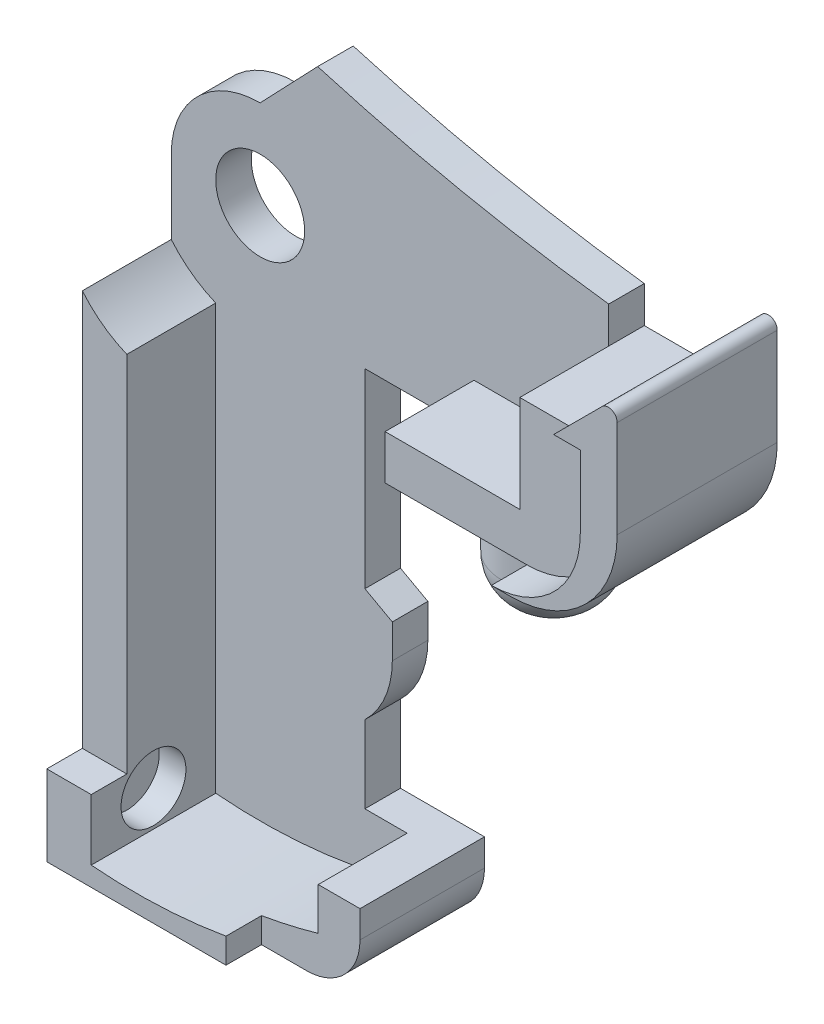
SolidWorks part; units mm, degrees
ref_plane "정면" through (0, 0, 0) normal (0, 0, 1) x (1, 0, 0)
ref_plane "윗면" through (0, 0, 0) normal (0, 1, 0) x (1, 0, 0)
ref_plane "우측면" through (0, 0, 0) normal (1, 0, 0) x (0, 0, -1)
sketch "스케치1" plane through (0, 0, 0) normal (0, 0, 1) x (1, 0, 0)
  line L0 (0, 5) -> (3.2319, 8.3833)
  line L1 (0, 5) -> (19.6, 5)
  line L2 (19.6, 5) -> (19.6, 2.9507)
  line L3 (19.6, 2.9507) -> (23.5, 2.9507)
  line L4 (23.5, 2.9507) -> (23.5, 4.0959)
  line L5 (23.5, 4.0959) -> (25, 4.0959)
  line L6 (25, 4.0959) -> (25, 0)
  line L7 (20, -5) -> (5.8894, -5)
  line L8 (5.8894, -5) -> (5.8894, -26.4376)
  line L9 (-5, -30.9618) -> (7.6137, -30.9618)
  line L10 (-5, -30.9618) -> (-5, 0)
  line L11 (10.6137, -27.9618) -> (10.6137, -26.4376)
  line L12 (10.6137, -26.4376) -> (5.8894, -26.4376)
  line L13 (5.8894, -26.4376) -> (8.2516, -26.4376)
  line L14 (19.6, 2.9507) -> (19.6, -2.5)
  line L15 (19.6, -2.5) -> (12.0232, -2.5)
  line L16 (-2.5, -4.3301) -> (-2.5, -26.4377)
  line L17 (-2.5, -29.8745) -> (-2.5, -26.4377)
  line L18 (-2.5, -26.4377) -> (-5, -26.4377)
  line L19 (5.0761, -29.546) -> (5.0761, -30.9618)
  line L20 (5.8894, -15.7188) -> (5.8894, -26.4376)
  line L21 (8.2649, -26.4376) -> (8.2649, -28.8171)
  line L22 (12.0232, -2.5) -> (12.0232, -5)
  line L23 (5.8894, -15.7188) -> (5.8894, -26.4376)
  line L24 (7.4303, -18.4599) -> (7.4303, -16.5644)
  line L25 (7.4303, -16.5644) -> (5.8894, -15.7188)
  line L26 (23.5, 4.0959) -> (26.2222, 6.8181)
  line L27 (27.0757, 6.4645) -> (27.0757, 1)
  line L28 (21.0757, -5) -> (20, -5)
  circle A0 centre (0, 0) radius 2.5
  circle A1 centre (0, 0) radius 5
  arc A2 (-2.5, -29.8745) -> (8.2649, -28.8171) centre (0, 0) ccw
  arc A3 (-5, -4.1533) -> (-2.5, -6) centre (0, 0) ccw
  arc A4 (19.6, 5) -> (3.2319, 8.3833) centre (32.2465, 107.4683) cw
  arc A5 (25, 0) -> (20, -5) centre (20, 0) cw
  arc A6 (7.4303, -18.4599) -> (5.8894, -22.0908) centre (2.3818, -18.4599) cw
  arc A7 (7.6137, -30.9618) -> (10.6137, -27.9618) centre (7.6137, -27.9618) ccw
  arc A8 (27.0757, 1) -> (21.0757, -5) centre (21.0757, 1) cw
  arc A9 (26.2222, 6.8181) -> (27.0757, 6.4645) centre (26.5757, 6.4645) cw
  point P48 (27.0757, 7.6716)
  dimension "D1" = 5
  dimension "D2" = 19.6
  dimension "D3" = 5
  dimension "D6" = 3
  dimension "D9" = 6
  dimension "D10" = 0.5
  dimension "D4" = 30
  dimension "D5" = 1.5
  dimension "D7" = 5.0568
  dimension "D8" = 45
extrude "보스-돌출3" add sketch "스케치1" along normal blind 9 contours A2 L17 L18 L10 L9 L19 | A9 L26 L5 L6 A5 L28 A8 L27 region at (-3.75, -26.5481, 0) region at (25.5751, 1.3496, 0)
extrude "보스-돌출4" add sketch "스케치1<7>" along normal blind 7 contours A2 L19 L9 L11 | L15 L7 L6 L5 L4 L3 L14 | A1 L10 L18 L16 region at (20.1009, -1.5137, 0) region at (-3.7678, -15.8289, 0) region at (8.3321, -29.0215, 0)
sketch "스케치1<7>" plane through (0, 0, 0) normal (0, 0, 1) x (1, 0, 0) same geometry as "스케치1"
extrude "보스-돌출5" add sketch "스케치1<8>" along normal blind 2 contours L17 A2 L11 L12 L8 L15 L14 L2 L1 A1 L10 L18 | A1 A0 | L10 A3 L16 A1 | L1 A4 L0 | A6 L23 region at (7.1251, 6.0723, 0) region at (5.4727, -10.5859, 0) region at (3.4355, 3.4355, 0) region at (-3.8947, -3.9886, 0) region at (6.5619, -18.6209, 0)
sketch "스케치1<8>" plane through (0, 0, 0) normal (0, 0, 1) x (1, 0, 0) same geometry as "스케치1"
sketch "스케치2" plane through (0, -5, 0) normal (0, -1, 0) x (1, 0, 0)
  circle A0 centre (18, 3.5) radius 2.9
  point P7 (22.0757, 3.5741)
  dimension "D1" = 5.8
extrude "보스-돌출6" add sketch "스케치2" along normal mid plane 4.9
sketch "스케치4" plane through (0, -7.45, 0) normal (0, -1, 0) x (1, 0, 0)
  circle A0 centre (18, 3.5) radius 2.9 construction
  circle A1 centre (18, 3.5) radius 2.9
extrude "보스-돌출7" add sketch "스케치4" along normal blind 2
fillet "필렛2" radius 2.4 1 edges at (18, -9.45, 0.6)
sketch "스케치5" plane through (-2.5, 0, 0) normal (1, 0, 0) x (0, 0, -1)
  line L0 (-9, -29.8745) -> (-2, -29.8745) construction
  circle A0 centre (-5.5, -27.8745) radius 1.825
  point P2 (-5.5, -29.8745)
  dimension "D1" = 3.65
  dimension "D2" = 2
extrude "컷-돌출1" cut sketch "스케치5" against normal blind 1.5
